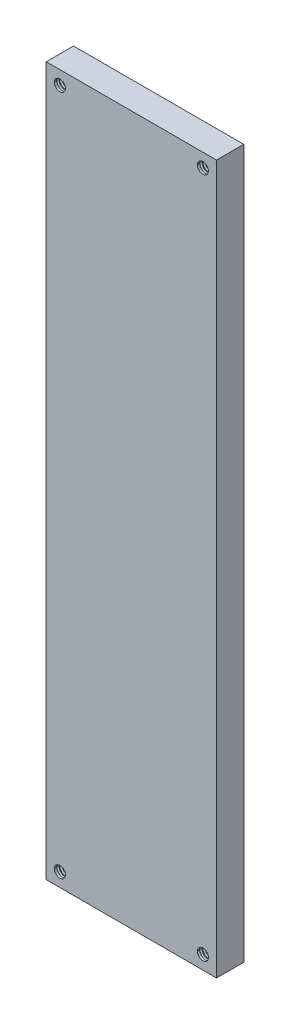
SolidWorks part; units mm, degrees
material "Cast Carbon Steel"
ref_plane "Front Plane" through (0, 0, 0) normal (0, 0, 1) x (1, 0, 0)
ref_plane "Top Plane" through (0, 0, 0) normal (0, 1, 0) x (1, 0, 0)
ref_plane "Right Plane" through (0, 0, 0) normal (1, 0, 0) x (0, 0, -1)
sketch "Sketch1" plane through (0, 0, 0) normal (0, 0, 1) x (1, 0, 0)
  line L1 (0, 0) -> (39.6875, 0)
  line L2 (0, 0) -> (0, 165.1)
  line L3 (0, 165.1) -> (39.6875, 165.1)
  line L4 (39.6875, 0) -> (39.6875, 165.1)
  circle A1 centre (36.5125, 161.925) radius 1.289
  circle A2 centre (36.5125, 3.175) radius 1.2891
  circle A3 centre (3.175, 3.175) radius 1.2891
  circle A4 centre (3.175, 161.925) radius 1.289
  dimension "D5" = 3.175
  dimension "D3" = 2.5781
  dimension "D6" = 2.5781
  dimension "D9" = 2.5781
  dimension "D12" = 2.5781
  dimension "D1" = 39.6875
  dimension "D2" = 165.1
  dimension "D4" = 3.175
  dimension "D7" = 3.175
  dimension "D8" = 3.175
  dimension "D10" = 3.175
  dimension "D11" = 3.175
  dimension "D13" = 3.175
  dimension "D14" = 3.175
extrude "Boss-Extrude1" add sketch "Sketch1" against normal blind 6.35
ref_plane "Plane1" through (0, 82.55, 0) normal (0, 1, 0) x (1, 0, 0)
thread "Thread1" pitch 0.635 method cut profile "Thread Profile1" start angle 0, offset 0, length 0, pitch 0.635, diameter 2.5781
ref_plane "Plane3" through (1.886, 161.925, 0) normal (0, -1, 0) x (-1, 0, 0)
sketch "Thread Profile1" plane through (1.886, 161.925, 0) normal (0, -1, 0) x (-1, 0, 0)
  line L0 (0, 0) -> (0, 0.635) construction
  line L1 (0, 0) -> (0.3437, 0.1984)
  line L2 (0.3437, 0.1984) -> (0.3437, 0.2778)
  line L3 (0.3437, 0.2778) -> (0, 0.4762)
  line L4 (0.3437, 0.2381) -> (0, 0.2381) construction
  line L11 (0, 0) -> (0, 0.4762)
  point P2 (0, 0)
  dimension "Pitch" = 0.635
  dimension "Profile_Angle" = 60
  dimension "Profile_Land" = 0.0794
  dimension "Profile_Height" = 0.3437
thread "Thread2" pitch 0.635 method cut profile "Thread Profile2" start angle 0, offset 0, length 0, pitch 0.635, diameter 2.5781
ref_plane "Plane4" through (35.2235, 161.925, 0) normal (0, -1, 0) x (-1, 0, 0)
sketch "Thread Profile2" plane through (35.2235, 161.925, 0) normal (0, -1, 0) x (-1, 0, 0)
  line L0 (0, 0) -> (0, 0.635) construction
  line L1 (0, 0) -> (0.3437, 0.1984)
  line L2 (0.3437, 0.1984) -> (0.3437, 0.2778)
  line L3 (0.3437, 0.2778) -> (0, 0.4762)
  line L4 (0.3437, 0.2381) -> (0, 0.2381) construction
  line L11 (0, 0) -> (0, 0.4762)
  point P2 (0, 0)
  dimension "Pitch" = 0.635
  dimension "Profile_Angle" = 60
  dimension "Profile_Land" = 0.0794
  dimension "Profile_Height" = 0.3437
thread "Thread3" pitch 0.635 method cut profile "Thread Profile4" start angle 0, offset 0, length 0, pitch 0.635, diameter 2.5781
ref_plane "Plane6" through (1.886, 3.175, 0) normal (0, -1, 0) x (-1, 0, 0)
sketch "Thread Profile4" plane through (1.886, 3.175, 0) normal (0, -1, 0) x (-1, 0, 0)
  line L0 (0, 0) -> (0, 0.635) construction
  line L1 (0, 0) -> (0.3437, 0.1984)
  line L2 (0.3437, 0.1984) -> (0.3437, 0.2778)
  line L3 (0.3437, 0.2778) -> (0, 0.4762)
  line L4 (0.3437, 0.2381) -> (0, 0.2381) construction
  line L11 (0, 0) -> (0, 0.4762)
  point P2 (0, 0)
  dimension "Pitch" = 0.635
  dimension "Profile_Angle" = 60
  dimension "Profile_Land" = 0.0794
  dimension "Profile_Height" = 0.3437
thread "Thread4" pitch 0.635 method cut profile "Thread Profile5" start angle 0, offset 0, length 0, pitch 0.635, diameter 2.5781
ref_plane "Plane7" through (35.2235, 3.175, 0) normal (0, -1, 0) x (-1, 0, 0)
sketch "Thread Profile5" plane through (35.2235, 3.175, 0) normal (0, -1, 0) x (-1, 0, 0)
  line L0 (0, 0) -> (0, 0.635) construction
  line L1 (0, 0) -> (0.3437, 0.1984)
  line L2 (0.3437, 0.1984) -> (0.3437, 0.2778)
  line L3 (0.3437, 0.2778) -> (0, 0.4762)
  line L4 (0.3437, 0.2381) -> (0, 0.2381) construction
  line L11 (0, 0) -> (0, 0.4762)
  point P2 (0, 0)
  dimension "Pitch" = 0.635
  dimension "Profile_Angle" = 60
  dimension "Profile_Land" = 0.0794
  dimension "Profile_Height" = 0.3437
